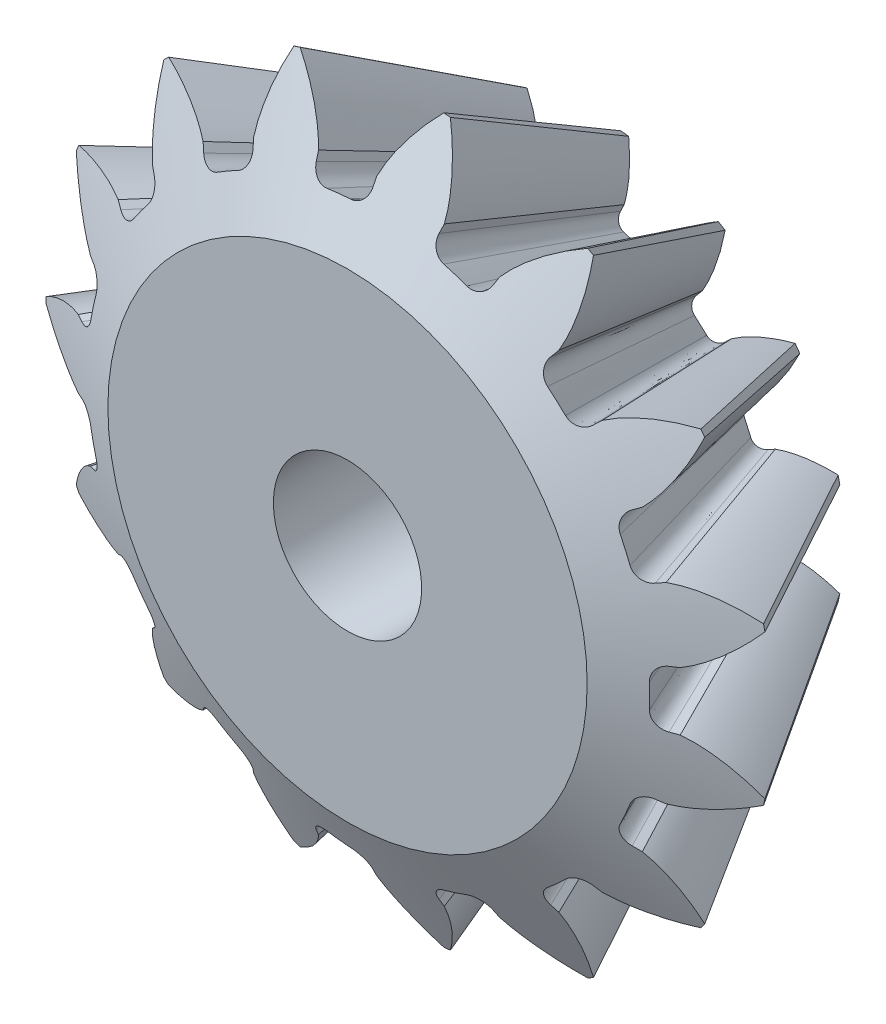
SolidWorks part; units mm, degrees
ref_plane "Front Plane" through (0, 0, 0) normal (0, 0, 1) x (1, 0, 0)
ref_plane "Top Plane" through (0, 0, 0) normal (0, 1, 0) x (1, 0, 0)
ref_plane "Right Plane" through (0, 0, 0) normal (1, 0, 0) x (0, 0, -1)
ref_axis "Gear Axis" through (0, 0, -1.8867) along (0, 0, 1)
sketch "Blank Sketch" plane through (0, 0, 0) normal (0, 1, 0) x (1, 0, 0)
  line L0 (0, 0) -> (0, -37.7336) construction
  line L1 (0, 0) -> (16.875, -33.75) construction
  line L2 (0, 0) -> (11.5084, -23.0169) construction
  line L3 (8.1015, -24.7204) -> (13.2341, -22.1541)
  line L4 (13.2341, -22.1541) -> (19.5818, -32.3966)
  line L5 (19.5818, -32.3966) -> (12.9285, -35.7233)
  line L6 (12.9285, -35.7233) -> (4, -35.7233)
  line L7 (4, -35.7233) -> (4, -24.7204)
  line L8 (4, -24.7204) -> (8.1015, -24.7204)
  line L9 (16.875, -33.75) -> (19.5818, -32.3966) construction
  line L10 (16.875, -33.75) -> (12.9285, -35.7233) construction
  line L11 (11.5084, -23.0169) -> (8.1015, -24.7204) construction
  dimension "Axis" = 37.7336
  dimension "Cone" = 26.565
  dimension "Heel" = 37.7336
  dimension "Toe Cone" = 26.565
  dimension "Toe" = 25.7336
  dimension "Heel Square" = 90
  dimension "Addendum" = 3.0263
  dimension "Root Square" = 90
  dimension "Heel Rim" = 4.4123
  dimension "Toe Square" = 90
  dimension "Toe Rim" = 3.8091
  dimension "Front Square" = 90
  dimension "Face" = 5.223
  dimension "Back" = 8.9285
  dimension "Front" = 4.1015
revolve "Blank" add sketch "Blank Sketch" angle 360 about L0
sketch "Cone Sketch" plane through (0, 0, 0) normal (0, 1, 0) x (1, 0, 0)
  line L0 (0, 0) -> (0, -37.7336) construction
  line L1 (0, 0) -> (17.8812, -35.7625)
  line L2 (0, 0) -> (10.5022, -21.0044)
  dimension "Axis" = 37.7336
  dimension "Toe Cone" = 26.565
  dimension "Heel Cone" = 26.565
  dimension "Heel" = 39.9836
  dimension "Toe" = 23.4836
ref_plane "Heel Plane" through (17.8812, 0, 35.7625) normal (0.4472, 0, 0.8944) x (0.8944, 0, -0.4472)
ref_plane "Toe Plane" through (10.5022, 0, 21.0044) normal (0.4472, 0, 0.8944) x (0.8944, 0, -0.4472)
sketch "Heel Section Sketch" plane through (17.8812, 0, 35.7625) normal (0.4472, 0, 0.8944) x (0.8944, 0, -0.4472)
  line L0 (0, 0) -> (-19.9918, 0) construction
  line L1 (-0.723, 1.6689) -> (-1.196, 1.6279)
  line L2 (-0.723, -1.6689) -> (-1.196, -1.6279)
  line L3 (4.7315, 6.5749) -> (4.7315, -6.5749)
  arc A0 (-1.196, 1.6279) -> (-2.0231, 0.6905) centre (-1.1178, 0.7253) ccw
  arc A1 (-2.0231, -0.6905) -> (-1.196, -1.6279) centre (-1.1178, -0.7253) ccw
  arc A2 (-2.0231, -0.6905) -> (-2.0231, 0.6905) centre (-19.9918, 0) ccw
  spline S0 degree 4 poles (-0.9812, 1.5906) (-0.9723, 1.593) (-0.9549, 1.5977) (-0.9258, 1.6056) (-0.8591, 1.6249) (-0.7519, 1.6586) (-0.6576, 1.6908) (-0.4447, 1.7698) (-0.2853, 1.8391) (-0.0621, 1.9399) (0.1331, 2.04) (0.3432, 2.1525) (0.539, 2.2671) (0.7384, 2.3893) (0.9305, 2.5149) (1.122, 2.6464) (1.3427, 2.8056) (1.6064, 3.0075) (1.9061, 3.2521) (2.2423, 3.5501) (2.575, 3.8654) (2.902, 4.2014) (3.2085, 4.5335) (3.5189, 4.8992) (3.7936, 5.2352) (4.0981, 5.6436) (4.3246, 5.954) (4.6361, 6.4235) (4.7882, 6.6622) (4.988, 6.9897) (5.0682, 7.1286) (5.1178, 7.2141) knots 0 0 0 0 0 0.003968 0.007937 0.015873 0.031746 0.049923 0.07426 0.101525 0.128791 0.156056 0.183322 0.210587 0.237852 0.265118 0.292383 0.319649 0.366669 0.4212 0.475731 0.530261 0.584792 0.639323 0.693854 0.748384 0.802915 0.857446 0.911977 0.955988 1 1 1 1 1 construction
  spline S1 degree 4 poles (-0.723, 1.6689) (-0.6909, 1.6798) (-0.6181, 1.7055) (-0.4447, 1.7698) (-0.2853, 1.8391) (-0.0621, 1.9399) (0.1331, 2.04) (0.3432, 2.1525) (0.539, 2.2671) (0.7384, 2.3893) (0.9305, 2.5149) (1.122, 2.6464) (1.3427, 2.8056) (1.6064, 3.0075) (1.9061, 3.2521) (2.2423, 3.5501) (2.575, 3.8654) (2.902, 4.2014) (3.2085, 4.5335) (3.5189, 4.8992) (3.7936, 5.2352) (4.0981, 5.6436) (4.3246, 5.954) (4.5701, 6.324) (4.6771, 6.489) (4.7315, 6.5749) knots 0.031746 0.031746 0.031746 0.031746 0.031746 0.049923 0.07426 0.101525 0.128791 0.156056 0.183322 0.210587 0.237852 0.265118 0.292383 0.319649 0.366669 0.4212 0.475731 0.530261 0.584792 0.639323 0.693854 0.748384 0.802915 0.857446 0.911977 0.911977 0.911977 0.911977 0.911977
  spline S2 degree 4 poles (-0.9812, -1.5906) (-0.9723, -1.593) (-0.9549, -1.5977) (-0.9258, -1.6056) (-0.8591, -1.6249) (-0.7519, -1.6586) (-0.6576, -1.6908) (-0.4447, -1.7698) (-0.2853, -1.8391) (-0.0621, -1.9399) (0.1331, -2.04) (0.3432, -2.1525) (0.539, -2.2671) (0.7384, -2.3893) (0.9305, -2.5149) (1.122, -2.6464) (1.3427, -2.8056) (1.6064, -3.0075) (1.9061, -3.2521) (2.2423, -3.5501) (2.575, -3.8654) (2.902, -4.2014) (3.2085, -4.5335) (3.5189, -4.8992) (3.7936, -5.2352) (4.0981, -5.6436) (4.3246, -5.954) (4.6361, -6.4235) (4.7882, -6.6622) (4.988, -6.9897) (5.0682, -7.1286) (5.1178, -7.2141) knots 0 0 0 0 0 0.003968 0.007937 0.015873 0.031746 0.049923 0.07426 0.101525 0.128791 0.156056 0.183322 0.210587 0.237852 0.265118 0.292383 0.319649 0.366669 0.4212 0.475731 0.530261 0.584792 0.639323 0.693854 0.748384 0.802915 0.857446 0.911977 0.955988 1 1 1 1 1 construction
  spline S3 degree 4 poles (-0.723, -1.6689) (-0.6909, -1.6798) (-0.6181, -1.7055) (-0.4447, -1.7698) (-0.2853, -1.8391) (-0.0621, -1.9399) (0.1331, -2.04) (0.3432, -2.1525) (0.539, -2.2671) (0.7384, -2.3893) (0.9305, -2.5149) (1.122, -2.6464) (1.3427, -2.8056) (1.6064, -3.0075) (1.9061, -3.2521) (2.2423, -3.5501) (2.575, -3.8654) (2.902, -4.2014) (3.2085, -4.5335) (3.5189, -4.8992) (3.7936, -5.2352) (4.0981, -5.6436) (4.3246, -5.954) (4.5701, -6.324) (4.6771, -6.489) (4.7315, -6.5749) knots 0.031746 0.031746 0.031746 0.031746 0.031746 0.049923 0.07426 0.101525 0.128791 0.156056 0.183322 0.210587 0.237852 0.265118 0.292383 0.319649 0.366669 0.4212 0.475731 0.530261 0.584792 0.639323 0.693854 0.748384 0.802915 0.857446 0.911977 0.911977 0.911977 0.911977 0.911977
  dimension "Root" = 17.982
  dimension "Fillet" = 0.906
  dimension "Centre" = 19.9918
sketch "Toe Section Sketch" plane through (10.5022, 0, 21.0044) normal (0.4472, 0, 0.8944) x (0.8944, 0, -0.4472)
  line L0 (0, 0) -> (-11.7418, 0) construction
  line L1 (-0.4246, 0.9802) -> (-0.7024, 0.9561)
  line L2 (-0.4246, -0.9802) -> (-0.7024, -0.9561)
  line L3 (2.779, 3.8617) -> (2.779, -3.8617)
  arc A0 (-0.7024, 0.9561) -> (-1.1882, 0.4056) centre (-0.6565, 0.426) ccw
  arc A1 (-1.1882, -0.4056) -> (-0.7024, -0.9561) centre (-0.6565, -0.426) ccw
  arc A2 (-1.1882, -0.4056) -> (-1.1882, 0.4056) centre (-11.7418, 0) ccw
  spline S0 degree 4 poles (-0.5779, 0.9336) (-0.5395, 0.9439) (-0.4628, 0.9671) (-0.4063, 0.9855) (-0.2638, 1.0385) (-0.1655, 1.0809) (-0.0378, 1.1389) (0.0791, 1.1984) (0.201, 1.2641) (0.317, 1.3316) (0.4334, 1.4032) (0.5466, 1.4772) (0.6589, 1.5543) (0.7886, 1.6479) (0.9434, 1.7664) (1.1195, 1.9101) (1.317, 2.0851) (1.5124, 2.2703) (1.7044, 2.4676) (1.8845, 2.6627) (2.0667, 2.8774) (2.2281, 3.0748) (2.4069, 3.3147) (2.54, 3.497) (2.7229, 3.7727) (2.8023, 3.8973) (2.9115, 4.0755) (2.9648, 4.1662) (2.9918, 4.2128) (3.0054, 4.2364) knots 0 0 0 0 0 0.031746 0.049923 0.07426 0.101525 0.128791 0.156056 0.183322 0.210587 0.237852 0.265118 0.292383 0.319649 0.366669 0.4212 0.475731 0.530261 0.584792 0.639323 0.693854 0.748384 0.802915 0.857446 0.911977 0.955988 0.977994 1 1 1 1 1 construction
  spline S1 degree 4 poles (-0.4246, 0.9802) (-0.4058, 0.9866) (-0.3618, 1.0021) (-0.2638, 1.0385) (-0.1655, 1.0809) (-0.0378, 1.1389) (0.0791, 1.1984) (0.201, 1.2641) (0.317, 1.3316) (0.4334, 1.4032) (0.5466, 1.4772) (0.6589, 1.5543) (0.7886, 1.6479) (0.9434, 1.7664) (1.1195, 1.9101) (1.317, 2.0851) (1.5124, 2.2703) (1.7044, 2.4676) (1.8845, 2.6627) (2.0667, 2.8774) (2.2281, 3.0748) (2.4069, 3.3147) (2.54, 3.497) (2.6841, 3.7143) (2.747, 3.8112) (2.779, 3.8617) knots 0.031746 0.031746 0.031746 0.031746 0.031746 0.049923 0.07426 0.101525 0.128791 0.156056 0.183322 0.210587 0.237852 0.265118 0.292383 0.319649 0.366669 0.4212 0.475731 0.530261 0.584792 0.639323 0.693854 0.748384 0.802915 0.857446 0.911977 0.911977 0.911977 0.911977 0.911977
  spline S2 degree 4 poles (-0.5779, -0.9336) (-0.5395, -0.9439) (-0.4628, -0.9671) (-0.4063, -0.9855) (-0.2638, -1.0385) (-0.1655, -1.0809) (-0.0378, -1.1389) (0.0791, -1.1984) (0.201, -1.2641) (0.317, -1.3316) (0.4334, -1.4032) (0.5466, -1.4772) (0.6589, -1.5543) (0.7886, -1.6479) (0.9434, -1.7664) (1.1195, -1.9101) (1.317, -2.0851) (1.5124, -2.2703) (1.7044, -2.4676) (1.8845, -2.6627) (2.0667, -2.8774) (2.2281, -3.0748) (2.4069, -3.3147) (2.54, -3.497) (2.7229, -3.7727) (2.8023, -3.8973) (2.9115, -4.0755) (2.9648, -4.1662) (2.9918, -4.2128) (3.0054, -4.2364) knots 0 0 0 0 0 0.031746 0.049923 0.07426 0.101525 0.128791 0.156056 0.183322 0.210587 0.237852 0.265118 0.292383 0.319649 0.366669 0.4212 0.475731 0.530261 0.584792 0.639323 0.693854 0.748384 0.802915 0.857446 0.911977 0.955988 0.977994 1 1 1 1 1 construction
  spline S3 degree 4 poles (-0.4246, -0.9802) (-0.4058, -0.9866) (-0.3618, -1.0021) (-0.2638, -1.0385) (-0.1655, -1.0809) (-0.0378, -1.1389) (0.0791, -1.1984) (0.201, -1.2641) (0.317, -1.3316) (0.4334, -1.4032) (0.5466, -1.4772) (0.6589, -1.5543) (0.7886, -1.6479) (0.9434, -1.7664) (1.1195, -1.9101) (1.317, -2.0851) (1.5124, -2.2703) (1.7044, -2.4676) (1.8845, -2.6627) (2.0667, -2.8774) (2.2281, -3.0748) (2.4069, -3.3147) (2.54, -3.497) (2.6841, -3.7143) (2.747, -3.8112) (2.779, -3.8617) knots 0.031746 0.031746 0.031746 0.031746 0.031746 0.049923 0.07426 0.101525 0.128791 0.156056 0.183322 0.210587 0.237852 0.265118 0.292383 0.319649 0.366669 0.4212 0.475731 0.530261 0.584792 0.639323 0.693854 0.748384 0.802915 0.857446 0.911977 0.911977 0.911977 0.911977 0.911977
  dimension "Root" = 10.5614
  dimension "Fillet" = 0.5321
  dimension "Centre" = 11.7418
loft "Tooth Space" cut profiles "Heel Section Sketch", "Toe Section Sketch"
pattern_circular "Teeth" count 15 over 360 about axis through (0, 0, -1.8867) along (0, 0, 1) of "Tooth Space"
equation "\"No. of Teeth\"= 15"
equation "\"Module\"= 2.25"
equation "\"Bore Diameter\"= 8"
equation "\"Pressure Angle\"= 20"
equation "\"Shaft Angle\"= 90"
equation "\"Mate Teeth\"= 30"
equation "\"Pitch Cone Angle\"= IIF ( ( \"Mate Teeth\" / \"No. of Teeth\" + cos ( \"Shaft Angle\" ) ) > 0 , atn ( sin ( \"Shaft Angle\" ) / ( \"Mate Teeth\" / \"No. of Teeth\" + cos ( \"Shaft Angle\" ) ) ) , 180 + atn ( sin ( \"Shaft Angle\" ) / ( \"Mate Teeth\" / \"No. of Teeth\" + cos ( \"Shaft Angle\" ) ) ) )"
equation "\"Mate Cone Angle\"= \"Shaft Angle\" - \"Pitch Cone Angle\""
equation "\"Addendum\"= IIF ( \"No. of Teeth\" >= \"Mate Teeth\" , 0.54 * \"Module\" + 0.46 * \"Module\" / ( ( \"No. of Teeth\" * cos ( \"Mate Cone Angle\" ) ) / ( \"Mate Teeth\" * cos ( \"Pitch Cone Angle\" ) ) ) , 2 * \"Module\" - ( 0.54 * \"Module\" + 0.46 * \"Module\" / ( ( \"Mate Teeth\" * cos ( \"Pitch Cone Angle\" ) ) / ( \"No. of Teeth\" * cos ( \"Mate Cone Angle\" ) ) ) ) )"
equation "\"Outer Diameter\"= \"No. of Teeth\" * \"Module\" + 2 * \"Addendum\" * cos ( \"Pitch Cone Angle\" )"
equation "\"Pitch Diameter\"= \"No. of Teeth\" * \"Module\""
equation "\"Backlash\"= 0.3 * \"Module\""
equation "\"Arc Length\"= ( ( \"Module\" * pi ) / 2 + \"Backlash\" - 2 * ( \"Addendum\" - \"Module\" ) * tan ( \"Pressure Angle\" ) )"
equation "\"Fillet Radius\"= 0.38 * \"Module\""
equation "\"Mate Addendum\"= 2 * \"Module\" - \"Addendum\""
equation "\"Dedendum\"= 2.188 * \"Module\" - \"Addendum\""
equation "\"Tooth Depth\"= \"Addendum\" + \"Dedendum\""
equation "\"Mate Dedendum\"= 2.188 * \"Module\" - \"Mate Addendum\""
equation "\"Face Width\"= 12"
equation "\"Cone Distance\"= \"Pitch Diameter\" / ( 2 * sin ( \"Pitch Cone Angle\" ) )"
equation "\"Dedendum Angle\"= atn ( \"Dedendum\" / \"Cone Distance\" )"
equation "\"Mate Dedendum Angle\"= atn ( \"Mate Dedendum\" / \"Cone Distance\" )"
equation "\"Face Angle\"= \"Pitch Cone Angle\" + \"Mate Dedendum Angle\""
equation "\"Root Angle\"= \"Pitch Cone Angle\" - \"Dedendum Angle\""
equation "\"Overrun\"= \"Module\""
equation "\"Back Cone Pitch Diameter\"= \"Pitch Diameter\" / cos ( \"Pitch Cone Angle\" )"
equation "\"Back Cone Outer Diameter\"= \"Back Cone Pitch Diameter\" + 2 * \"Addendum\""
equation "\"Root Diameter\"= \"Back Cone Outer Diameter\" - 2 * \"Tooth Depth\""
equation "\"Base Diameter\"= \"Back Cone Pitch Diameter\" * cos ( \"Pressure Angle\" )"
equation "\"Base Radius\"= \"Base Diameter\" / 2"
equation "\"Tooth Thickness\"= \"Module\" * pi - \"Arc Length\""
equation "\"Half Space Angle\"= ( \"Arc Length\" / \"Back Cone Pitch Diameter\" ) * 180 / pi"
equation "\"Involute Fn\"= tan ( \"Pressure Angle\" ) - \"Pressure Angle\" * pi / 180"
equation "\"Flank Offset\"= \"Arc Length\" / \"Back Cone Pitch Diameter\" - \"Involute Fn\""
equation "\"Tip Cap Diameter\"= \"Back Cone Outer Diameter\" + 2 * \"Module\""
equation "\"Flank Start Diameter\"= IIF ( \"Base Diameter\" >= ( \"Root Diameter\" + 3 * \"Fillet Radius\" ) , \"Base Diameter\" , \"Root Diameter\" + 3 * \"Fillet Radius\" )"
equation "\"Involute t1\"= ( abs ( ( \"Flank Start Diameter\" / \"Base Diameter\" ) ^ 2 - 1 ) ) ^ 0.5"
equation "\"Involute t2\"= ( abs ( ( \"Tip Cap Diameter\" / \"Base Diameter\" ) ^ 2 - 1 ) ) ^ 0.5"
equation "\"Flank Arc Radius\"= ( \"Back Cone Pitch Diameter\" / 2 ) * sin ( \"Pressure Angle\" )"
equation "\"Flank Centre Angle\"= \"Half Space Angle\" + \"Pressure Angle\""
equation "\"Heel Distance\"= \"Cone Distance\" + \"Overrun\""
equation "\"Toe Distance\"= \"Cone Distance\" - \"Face Width\" - \"Overrun\""
equation "\"Heel Scale\"= \"Heel Distance\" / \"Cone Distance\""
equation "\"Toe Scale\"= \"Toe Distance\" / \"Cone Distance\""
equation "\"Heel Virtual Radius\"= \"Heel Distance\" * tan ( \"Pitch Cone Angle\" )"
equation "\"Toe Virtual Radius\"= \"Toe Distance\" * tan ( \"Pitch Cone Angle\" )"
equation "\"Axis@Blank Sketch\"= \"Cone Distance\""
equation "\"Cone@Blank Sketch\"= \"Pitch Cone Angle\""
equation "\"Heel@Blank Sketch\"= \"Cone Distance\""
equation "\"Toe Cone@Blank Sketch\"= \"Pitch Cone Angle\""
equation "\"Toe@Blank Sketch\"= \"Cone Distance\" - \"Face Width\""
equation "\"Addendum@Blank Sketch\"= \"Addendum\""
equation "\"Heel Rim@Blank Sketch\"= \"Dedendum\" + \"Module\" / cos ( \"Pitch Cone Angle\" )"
equation "\"Toe Rim@Blank Sketch\"= \"Dedendum\" - \"Face Width\" * tan ( \"Dedendum Angle\" ) + \"Module\" / cos ( \"Pitch Cone Angle\" )"
equation "\"Face@Blank Sketch\"= \"Mate Dedendum Angle\""
equation "\"Back@Blank Sketch\"= \"Cone Distance\" * sin ( \"Pitch Cone Angle\" ) - \"Dedendum\" * cos ( \"Pitch Cone Angle\" ) - \"Module\" - \"Bore Diameter\" / 2"
equation "\"Front@Blank Sketch\"= ( \"Cone Distance\" - \"Face Width\" ) * sin ( \"Pitch Cone Angle\" ) - ( \"Dedendum\" - \"Face Width\" * tan ( \"Dedendum Angle\" ) + \"Module\" / cos ( \"Pitch Cone Angle\" ) ) * cos ( \"Pitch Cone Angle\" ) - \"Bore Diameter\" / 2"
equation "\"Axis@Cone Sketch\"= \"Cone Distance\""
equation "\"Heel Cone@Cone Sketch\"= \"Pitch Cone Angle\""
equation "\"Heel@Cone Sketch\"= \"Heel Distance\""
equation "\"Toe Cone@Cone Sketch\"= \"Pitch Cone Angle\""
equation "\"Toe@Cone Sketch\"= \"Toe Distance\""
equation "\"Centre@Heel Section Sketch\"= \"Heel Virtual Radius\""
equation "\"Root@Heel Section Sketch\"= ( \"Root Diameter\" / 2 ) * \"Heel Scale\""
equation "\"Fillet@Heel Section Sketch\"= ( \"Fillet Radius\" ) * \"Heel Scale\""
equation "\"Centre@Toe Section Sketch\"= \"Toe Virtual Radius\""
equation "\"Root@Toe Section Sketch\"= ( \"Root Diameter\" / 2 ) * \"Toe Scale\""
equation "\"Fillet@Toe Section Sketch\"= ( \"Fillet Radius\" ) * \"Toe Scale\""
equation "\"Count@Teeth\"= \"No. of Teeth\""
